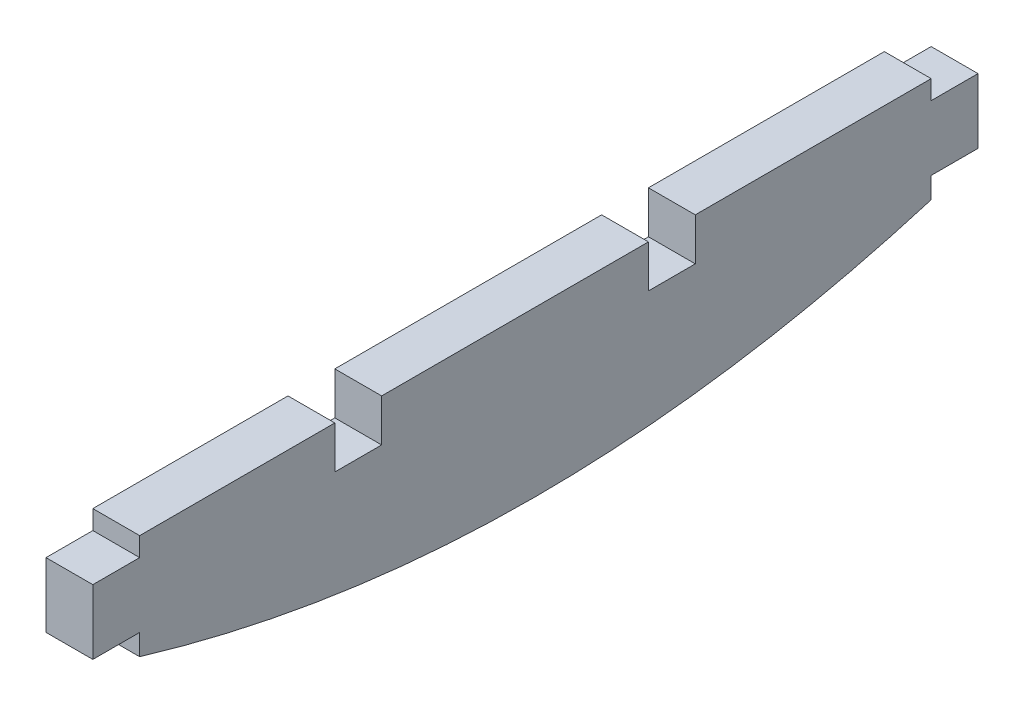
SolidWorks part; units mm, degrees
ref_plane "Přední rovina" through (0, 0, 0) normal (0, 0, 1) x (1, 0, 0)
ref_plane "Horní rovina" through (0, 0, 0) normal (0, 1, 0) x (1, 0, 0)
ref_plane "Pravá rovina" through (0, 0, 0) normal (1, 0, 0) x (0, 0, -1)
sketch "Skica3" plane through (0, 0, 0) normal (1, 0, 0) x (0, 0, -1)
  line L0 (-56.0884, 0) -> (54.1991, 0) construction
  line L1 (-18.8481, -2.075) -> (-15.8481, -2.075)
  line L2 (-18.8481, -2.075) -> (-18.8481, 2.075)
  line L3 (-18.8481, 2.075) -> (-15.8481, 2.075)
  line L5 (-18.8481, -2.075) -> (-15.8481, 2.075) construction
  line L6 (-18.8481, 2.075) -> (-15.8481, -2.075) construction
  line L8 (-15.8481, 3.295) -> (34.8519, 3.295)
  line L9 (-15.8481, 3.295) -> (-15.8481, -3.425)
  line L10 (-15.8481, -3.425) -> (34.8519, -3.425)
  line L11 (34.8519, 3.295) -> (34.8519, -3.425)
  line L12 (34.8519, -2.075) -> (37.8519, -2.075)
  line L14 (34.8519, 2.075) -> (37.8519, 2.075)
  line L15 (37.8519, -2.075) -> (37.8519, 2.075)
  line L16 (34.8519, -2.075) -> (37.8519, 2.075) construction
  line L17 (34.8519, 2.075) -> (37.8519, -2.075) construction
  spline S0 degree 2 poles (34.8519, -3.425) (9.5019, -11.0261) (-15.8481, -3.425) knots 0 0 0 1 1 1
  point P0 (-17.3481, 0)
  point P12 (36.3519, 0)
  point P17 (9.5019, -3.425)
  point P20 (9.5019, -7.2255)
  point P21 (9.5019, -7.2255)
  dimension "D1" = 3
  dimension "D2" = 4.15
  dimension "D3" = 2.075
  dimension "D4" = 1.22
  dimension "D5" = 50.7
  dimension "D6" = 1.35
  dimension "D7" = 3
  dimension "D8" = 4.15
  dimension "D9" = 1.5
  dimension "D10" = 1.22
extrude "Přidat vysunutím1" add sketch "Skica3" along normal blind 3 contours L9 L8 L11 L10
extrude "Přidat vysunutím2" add sketch "Skica3<3>" along normal blind 3 contours L12 L15 L14 L11 region at (0, 0, -36.3519)
sketch "Skica3<3>" plane through (0, 0, 0) normal (1, 0, 0) x (0, 0, -1) same geometry as "Skica3"
extrude "Přidat vysunutím3" add sketch "Skica3<4>" along normal blind 3 contours L9 L3 L2 L1 region at (0, 0, 17.3481)
sketch "Skica3<4>" plane through (0, 0, 0) normal (1, 0, 0) x (0, 0, -1) same geometry as "Skica3"
extrude "Přidat vysunutím4" add sketch "Skica3<6>" along normal blind 3 contours S0 L10 region at (0, -4.9452, -9.5019)
sketch "Skica3<6>" plane through (0, 0, 0) normal (1, 0, 0) x (0, 0, -1) same geometry as "Skica3"
sketch "Skica5" plane through (3, 0, 0) normal (1, 0, 0) x (0, 0, -1)
  line L0 (-15.8481, 3.295) -> (-15.8481, 2.075) construction
  line L1 (-3.3481, 0.575) -> (-0.3481, 0.575)
  line L2 (-3.3481, 0.575) -> (-3.3481, 5.9956)
  line L3 (-3.3481, 5.9956) -> (-0.3481, 5.9956)
  line L4 (-0.3481, 0.575) -> (-0.3481, 5.9956)
  line L6 (16.7419, 0.575) -> (19.7419, 0.575)
  line L7 (16.7419, 0.575) -> (16.7419, 5.9956)
  line L8 (16.7419, 5.9956) -> (19.7419, 5.9956)
  line L9 (19.7419, 0.575) -> (19.7419, 5.9956)
  line L10 (-15.8481, 3.295) -> (34.8519, 3.295) construction
  dimension "D1" = 12.5
  dimension "D2" = 3
  dimension "D3" = 32.59
  dimension "D4" = 3
  dimension "D5" = 2.72
  dimension "D6" = 2.72
extrude "Odebrat vysunutím1" cut sketch "Skica5" against normal blind 3 contours L2 L1 L4 L3 | L7 L6 L9 L8
